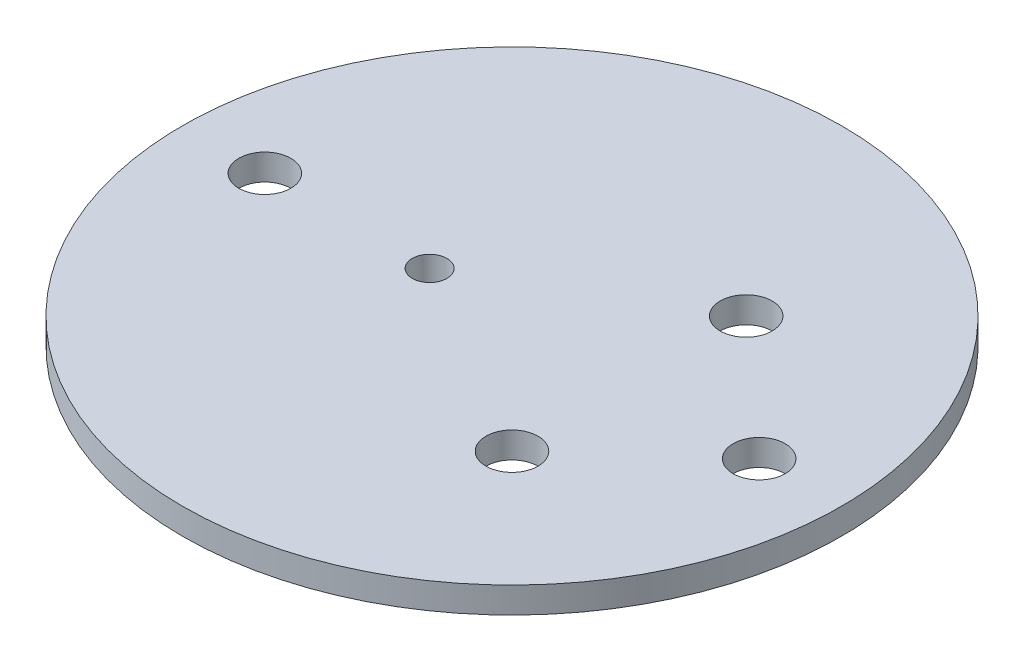
SolidWorks part; units mm, degrees
ref_plane "Front Plane" through (0, 0, 0) normal (0, 0, 1) x (1, 0, 0)
ref_plane "Top Plane" through (0, 0, 0) normal (0, 1, 0) x (1, 0, 0)
ref_plane "Right Plane" through (0, 0, 0) normal (1, 0, 0) x (0, 0, -1)
sketch "Sketch1" plane through (0, 0, 0) normal (0, 1, 0) x (1, 0, 0)
  line L0 (-28.5, 0) -> (28.5, 0) construction
  line L1 (13.5, 13.5) -> (13.5, -13.5) construction
  circle A0 centre (0, 0) radius 38
  circle A1 centre (28.5, 0) radius 3
  circle A2 centre (-28.5, 0) radius 3
  circle A3 centre (13.5, 13.5) radius 3
  circle A4 centre (13.5, -13.5) radius 3
  circle A5 centre (-28.5, 0) radius 6.25 construction
  circle A6 centre (13.5, 13.5) radius 12.5 construction
  circle A7 centre (13.5, -13.5) radius 12.5 construction
  circle A8 centre (28.5, 0) radius 6.25 construction
  circle A9 centre (-9.5, 0) radius 2
  circle A10 centre (-9.5, 0) radius 12.5 construction
  point P2 (13.5, 0)
  point P11 (0, 0)
  dimension "D1" = 76
  dimension "D3" = 6
  dimension "D4" = 13.5
  dimension "D5" = 6
  dimension "D6" = 12.5
  dimension "D7" = 25
  dimension "D9" = 4
  dimension "D10" = 25
  dimension "D2" = 57
  dimension "D8" = 13.5
  dimension "D11" = 9.5
extrude "Boss-Extrude1" add sketch "Sketch1" against normal blind 3 contours A0 A4 A3 A2 A1 region at (-0.146, 0, 0)
